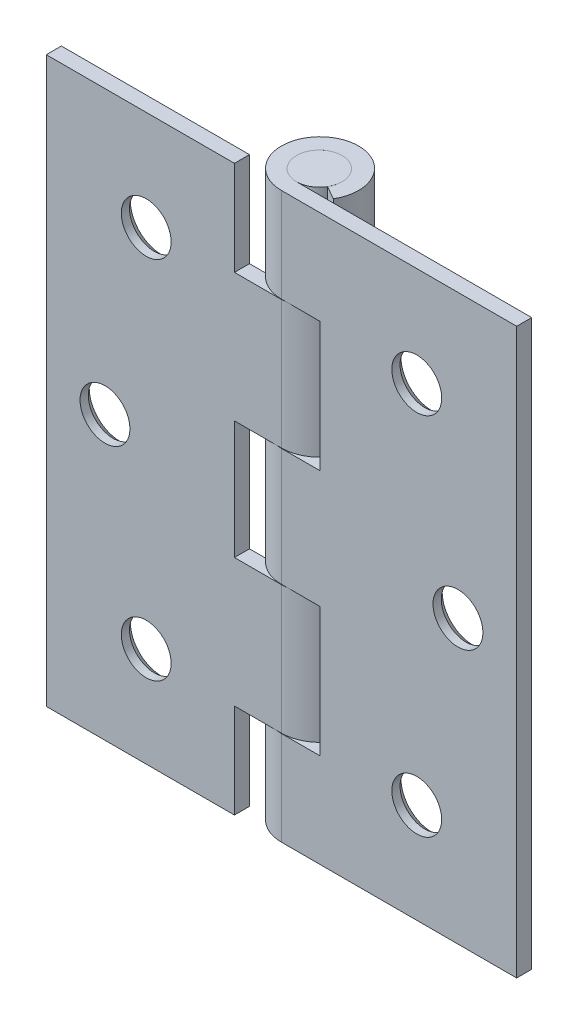
SolidWorks part; units mm, degrees
ref_plane "Front" through (0, 0, 0) normal (0, 0, 1) x (1, 0, 0)
ref_plane "Top" through (0, 0, 0) normal (0, 1, 0) x (1, 0, 0)
ref_plane "Right" through (0, 0, 0) normal (1, 0, 0) x (0, 0, -1)
sketch "Sketch1" plane through (0, 0, 0) normal (0, 1, 0) x (1, 0, 0)
  line L0 (0, 0) -> (4.4648, -2.5777) construction
  line L1 (0, -3.0734) -> (31.75, -3.0734)
  line L2 (2.6616, -1.5367) -> (4.4648, -2.5777)
  line L3 (0, -5.1054) -> (31.75, -5.1054)
  line L4 (31.75, -3.0734) -> (31.75, -5.1054)
  arc A0 (2.6616, -1.5367) -> (0, -3.0734) centre (0, 0) ccw
  arc A2 (4.4648, -2.5777) -> (0, -5.1054) centre (0, 0.1016) ccw
  dimension "D5" = 10.414
  dimension "D1" = 30
  dimension "D2" = 31.75
extrude "Extrude1" add sketch "Sketch1" along normal mid plane 76.2
sketch "Sketch2" plane through (0, 0, 3.0734) normal (0, 0, -1) x (-1, 0, 0)
  line L0 (5.207, 38.1) -> (5.207, 25.4)
  line L1 (5.207, 25.4) -> (-5.207, 25.4)
  line L2 (-5.207, 25.4) -> (-5.207, 7.9375)
  line L3 (-5.207, 7.9375) -> (5.207, 7.9375)
  line L4 (5.207, 7.9375) -> (5.207, -7.9375)
  line L5 (5.207, -7.9375) -> (-5.207, -7.9375)
  line L6 (-5.207, -7.9375) -> (-5.207, -25.4)
  line L7 (-5.207, -25.4) -> (5.207, -25.4)
  line L8 (5.207, -25.4) -> (5.207, -38.1)
  line L9 (-31.75, -38.1) -> (0, -38.1) construction
  line L10 (-31.75, 38.1) -> (0, 38.1) construction
  line L13 (-5.207, 38.1) -> (-5.207, -38.1) construction
  line L14 (5.207, -38.1) -> (5.207, 38.1) construction
  point P15 (5.207, 0)
  point P20 (-5.207, 16.6688)
  point P21 (-5.207, -16.6688)
  dimension "D1" = 15.875
  dimension "D2" = 12.7
extrude "Cut-Extrude1" cut sketch "Sketch2" against normal through all and the other way through all
ref_plane "Plane1" through (0, 16.6688, 0) normal (0, 1, 0) x (-1, 0, 0)
sketch "Sketch3" plane through (0, 16.6688, 0) normal (0, 1, 0) x (-1, 0, 0)
  line L0 (0, 6.7888) -> (0, -8.653) construction
  line L1 (31.75, 5.1054) -> (31.75, 3.0734)
  line L2 (2.6616, 1.5367) -> (4.4343, 2.6278)
  line L3 (0, 3.0734) -> (31.75, 3.0734)
  line L4 (-2.6616, 1.5367) -> (-4.4648, 2.5777)
  line L5 (0, 5.1054) -> (-31.75, 5.1054)
  line L6 (-31.75, 5.1054) -> (-31.75, 3.0734)
  line L7 (-31.75, 3.0734) -> (0, 3.0734)
  line L9 (31.75, 5.1054) -> (0, 5.1054)
  arc A2 (-2.6616, 1.5367) -> (0, 3.0734) centre (0, 0) ccw
  arc A3 (-4.4648, 2.5777) -> (0, 5.1054) centre (0, -0.1016) ccw
  arc A4 (0, 3.0734) -> (2.6616, 1.5367) centre (0, 0) ccw
  arc A5 (0, 5.1054) -> (4.4343, 2.6278) centre (0, -0.1016) ccw
  dimension "D1" = 0
extrude "Extrude2" add sketch "Sketch3" along normal offset from surface 0.0508 and the other way offset from surface 0.0508 up to face at (1.6459, 25.4, 1.1718) other way up to face at (1.6459, 7.9375, 1.1718)
ref_plane "Plane2" through (0, -16.6688, 0) normal (0, 1, 0) x (-1, 0, 0)
sketch "Sketch4" plane through (0, -16.6688, 0) normal (0, 1, 0) x (-1, 0, 0)
  line L4 (0, 3.0734) -> (31.75, 3.0734)
  line L5 (31.75, 3.0734) -> (31.75, 5.1054)
  line L6 (31.75, 5.1054) -> (0, 5.1054)
  line L7 (4.4343, 2.6278) -> (2.6616, 1.5367)
  line L8 (0, 3.0734) -> (31.75, 3.0734)
  line L9 (31.75, 3.0734) -> (31.75, 5.1054)
  line L10 (31.75, 5.1054) -> (0, 5.1054)
  line L11 (4.4343, 2.6278) -> (2.6616, 1.5367)
  arc A2 (0, 5.1054) -> (4.4343, 2.6278) centre (0, -0.1016) ccw
  arc A3 (0, 3.0734) -> (2.6616, 1.5367) centre (0, 0) ccw
  arc A4 (0, 5.1054) -> (4.4343, 2.6278) centre (0, -0.1016) ccw
  arc A5 (0, 3.0734) -> (2.6616, 1.5367) centre (0, 0) ccw
  dimension "D1" = 0
extrude "Extrude3" add sketch "Sketch4" along normal offset from surface 0.0508 and the other way offset from surface 0.0508 up to face at (1.6459, -7.9375, 1.1718) other way up to face at (1.6459, -25.4, 1.1718)
sketch "Sketch5" plane through (0, -16.6688, 0) normal (0, 1, 0) x (-1, 0, 0)
  line L0 (31.75, 3.0734) -> (0, 3.0734) construction
  line L1 (31.75, 5.1054) -> (6.35, 5.1054)
  line L2 (31.75, 5.1054) -> (31.75, 3.0734)
  line L3 (31.75, 3.0734) -> (6.35, 3.0734)
  line L4 (6.35, 5.1054) -> (6.35, 3.0734)
  dimension "D1" = 25.4
extrude "Extrude4" add sketch "Sketch5" along normal up to surface (54.7687 mm away) and the other way up to surface (21.4312 mm away) up to face at (10.4935, 38.1, 1.1718) other way up to face at (10.4935, -38.1, 1.1718)
sketch "Sketch6" plane through (0, 0, 0) normal (0, 0, 1) x (1, 0, 0)
  line L0 (0, 42.3616) -> (0, -43.1897) construction
  line L2 (0, 38.1) -> (-3.0734, 38.1)
  line L3 (0, 38.1) -> (0, -38.1)
  line L4 (0, -38.1) -> (-3.0734, -38.1)
  line L5 (-3.0734, 38.1) -> (-3.0734, -38.1)
  line L6 (0, -38.1) -> (31.75, -38.1) construction
  line L7 (5.207, 38.1) -> (-5.207, 38.1) construction
  line L8 (0, 38.1) -> (31.75, 38.1) construction
  dimension "D1" = 6.1468
revolve "Revolve1" add sketch "Sketch6" angle 360 about L0
hole_wizard "CSK for #8 Flat Head Machine Screw2" positions "Sketch10" profile "Sketch9" countersink size "#8" standard "Ansi Inch"
sketch "Sketch10" plane through (0, 0, 3.0734) normal (0, 0, -1) x (-1, 0, 0)
  line L0 (-8.3232, 0) -> (11.9672, 0) construction
  line L1 (31.75, 38.1) -> (31.75, -38.1) construction
  line L2 (0, 11.4703) -> (0, -6.6669) construction
  point P0 (23.8252, 0)
  point P4 (18.2626, 24.638)
  point P5 (18.2626, -24.638)
  point P10 (-18.2626, -24.638)
  point P11 (-23.8252, 0)
  point P12 (-18.2626, 24.638)
  dimension "D1" = 49.276
  dimension "D2" = 7.9248
  dimension "D3" = 5.5626
sketch "Sketch9" plane through (-23.8252, 0, 3.0734) normal (1, 0, 0) x (0, 1, 0)
  line L0 (0, 0) -> (0, 4.1302)
  line L1 (0, 4.1302) -> (3.3655, 2.108)
  line L2 (3.3655, 2.108) -> (3.3655, 0.9204)
  line L3 (3.3655, 0.9204) -> (4.1656, 0)
  line L5 (4.1656, 0) -> (0, 0)
  line L6 (-3.3655, 0.9204) -> (-4.1656, 0) construction
  line L10 (0, 4.1302) -> (-3.3655, 2.108) construction
  line L11 (0, -6.35) -> (0, 107.95) construction
  dimension "Hole Dia." = 6.731
  dimension "Hole Depth" = 2.108
  dimension "Near C'Sink Dia." = 8.3312
  dimension "Near C'Sink Angle" = 82
  dimension "Drill Angle" = 118
sketch "Sketch11" plane through (0, 38.1, 0) normal (0, 1, 0) x (1, 0, 0)
  line L0 (0, 5.3086) -> (0, -5.1054) construction
  arc A1 (4.4648, -2.5777) -> (0, -5.1054) centre (0, 0.1016) ccw construction
  point P7 (0, 5.3086)
ref_plane "Contact Plane 1" through (0, 0, 5.1054) normal (0, 0, 1) x (1, 0, 0)
ref_axis "Axis1" through (0, 41.91, 0) along (0, -1, 0)
sketch "Sketch12" plane through (0, 0, 0) normal (0, 1, 0) x (1, 0, 0)
  line L4 (-6.35, -3.0734) -> (-31.75, -3.0734)
  line L5 (-31.75, -3.0734) -> (-31.75, -5.1054)
  line L6 (-31.75, -5.1054) -> (-6.35, -5.1054)
  line L7 (-6.35, -5.1054) -> (-6.35, -3.0734)
  line L8 (-6.35, -3.0734) -> (-31.75, -3.0734)
  line L9 (-31.75, -3.0734) -> (-31.75, -5.1054)
  line L10 (-31.75, -5.1054) -> (-6.35, -5.1054)
  line L11 (-6.35, -5.1054) -> (-6.35, -3.0734)
  line L12 (-6.35, -3.0734) -> (-6.35, -5.1054)
  line L13 (-6.35, -5.1054) -> (0, -5.1054)
  line L14 (-4.4343, -2.6278) -> (-2.6616, -1.5367)
  line L15 (0, -3.0734) -> (-6.35, -3.0734)
  line L16 (-6.35, -3.0734) -> (-6.35, -5.1054)
  line L17 (-6.35, -5.1054) -> (0, -5.1054)
  line L18 (-4.4343, -2.6278) -> (-2.6616, -1.5367)
  line L19 (0, -3.0734) -> (-6.35, -3.0734)
  arc A0 (4.4648, -2.5777) -> (0, -5.1054) centre (0, 0.1016) ccw construction
  arc A1 (4.4648, -2.5777) -> (0, -5.1054) centre (0, 0.1016) ccw
  arc A4 (0, -5.1054) -> (-4.4343, -2.6278) centre (0, 0.1016) ccw
  arc A5 (0, -3.0734) -> (-2.6616, -1.5367) centre (0, 0) ccw
  arc A6 (0, -5.1054) -> (-4.4343, -2.6278) centre (0, 0.1016) ccw
  arc A7 (0, -3.0734) -> (-2.6616, -1.5367) centre (0, 0) ccw
  dimension "D1" = 0
  dimension "D2" = 0
extrude "Cut-Extrude2" [suppressed] cut sketch "Sketch12" against normal through all both and the other way through all contours A1 L19 L11 L17 | L10 L11 L8 L9
sketch "Sketch13" plane through (0, 0, 0) normal (0, 1, 0) x (1, 0, 0)
  line L0 (-6.35, -3.0734) -> (-6.35, -5.1054) construction
  line L1 (-6.35, -5.1054) -> (0, -5.1054) construction
  line L2 (-4.4343, -2.6278) -> (-2.6616, -1.5367) construction
  line L3 (0, -3.0734) -> (-6.35, -3.0734) construction
  line L4 (2.6616, -1.5367) -> (4.4648, -2.5777) construction
  line L5 (0, -5.1054) -> (31.75, -5.1054) construction
  line L6 (31.75, -5.1054) -> (31.75, -3.0734) construction
  line L7 (31.75, -3.0734) -> (0, -3.0734) construction
  line L8 (-6.35, -3.0734) -> (-6.35, -5.1054)
  line L9 (-6.35, -5.1054) -> (0, -5.1054)
  line L10 (-4.4343, -2.6278) -> (-2.6616, -1.5367)
  line L11 (0, -3.0734) -> (-6.35, -3.0734)
  line L12 (2.6616, -1.5367) -> (4.4648, -2.5777)
  line L13 (0, -5.1054) -> (31.75, -5.1054)
  line L14 (31.75, -5.1054) -> (31.75, -3.0734)
  line L15 (31.75, -3.0734) -> (0, -3.0734)
  arc A0 (0, -5.1054) -> (-4.4343, -2.6278) centre (0, 0.1016) ccw construction
  arc A1 (0, -3.0734) -> (-2.6616, -1.5367) centre (0, 0) ccw construction
  arc A2 (2.6616, -1.5367) -> (0, -3.0734) centre (0, 0) ccw construction
  arc A3 (4.4648, -2.5777) -> (0, -5.1054) centre (0, 0.1016) ccw construction
  arc A4 (0, -5.1054) -> (-4.4343, -2.6278) centre (0, 0.1016) ccw
  arc A5 (0, -3.0734) -> (-2.6616, -1.5367) centre (0, 0) ccw
  arc A6 (2.6616, -1.5367) -> (0, -3.0734) centre (0, 0) ccw
  arc A7 (4.4648, -2.5777) -> (0, -5.1054) centre (0, 0.1016) ccw
extrude "Cut-Extrude3" [suppressed] cut sketch "Sketch13" against normal through all both and the other way through all contours A4 L13 L14 L15
equation "\"D1@Sketch6\"=\"D3@Sketch1\""
